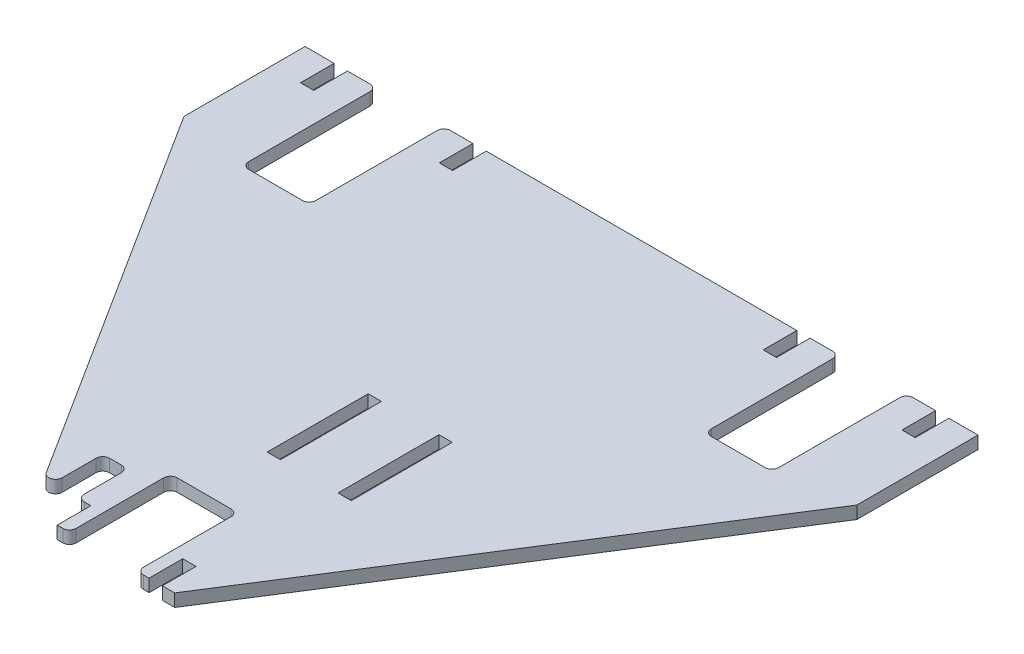
SolidWorks part; units mm, degrees
material "Corrugated Paper"
ref_plane "Front Plane" through (0, 0, 0) normal (0, 0, 1) x (1, 0, 0)
ref_plane "Top Plane" through (0, 0, 0) normal (0, 1, 0) x (1, 0, 0)
ref_plane "Right Plane" through (0, 0, 0) normal (1, 0, 0) x (0, 0, -1)
sketch "Sketch1" plane through (0, 0, 0) normal (0, 1, 0) x (1, 0, 0)
  line L0 (0, 0) -> (0, -142.875) construction
  line L1 (12.7, -63.5) -> (-12.7, -63.5)
  line L2 (-12.7, -63.5) -> (-12.7, -101.6)
  line L3 (-12.7, -101.6) -> (-17.3355, -101.6)
  line L4 (-26.9875, -101.6) -> (-127, 55.88)
  line L5 (-127, 55.88) -> (-127, 101.6)
  line L6 (-127, 101.6) -> (-116.0145, 101.6)
  line L7 (-100.0125, 101.6) -> (-100.0125, 50.8)
  line L9 (-100.0125, 50.8) -> (-74.6125, 50.8)
  line L10 (-74.6125, 50.8) -> (-74.6125, 101.6)
  line L11 (-74.6125, 101.6) -> (-63.627, 101.6)
  line L13 (74.6125, 50.8) -> (74.6125, 101.6)
  line L14 (100.0125, 50.8) -> (74.6125, 50.8)
  line L15 (100.0125, 101.6) -> (100.0125, 50.8)
  line L16 (127, 101.6) -> (116.0145, 101.6)
  line L17 (127, 55.88) -> (127, 101.6)
  line L18 (26.9875, -101.6) -> (127, 55.88)
  line L19 (12.7, -101.6) -> (17.3355, -101.6)
  line L20 (12.7, -63.5) -> (12.7, -101.6)
  line L21 (-127, 101.6) -> (127, -101.6) construction
  line L22 (-22.352, -101.6) -> (-26.9875, -101.6)
  line L24 (-22.352, -101.6) -> (-22.352, -88.9)
  line L25 (-22.352, -88.9) -> (-17.3355, -88.9)
  line L26 (-17.3355, -101.6) -> (-17.3355, -88.9)
  line L27 (22.352, -101.6) -> (22.352, -88.9)
  line L28 (22.352, -88.9) -> (17.3355, -88.9)
  line L29 (17.3355, -101.6) -> (17.3355, -88.9)
  line L30 (22.352, -101.6) -> (26.9875, -101.6)
  line L31 (-87.3125, 50.8) -> (-87.3125, 101.6) construction
  line L32 (-110.998, 101.6) -> (-100.0125, 101.6)
  line L34 (-116.0145, 101.6) -> (-116.0145, 88.9)
  line L35 (-116.0145, 88.9) -> (-110.998, 88.9)
  line L36 (-110.998, 101.6) -> (-110.998, 88.9)
  line L37 (-58.6105, 101.6) -> (-58.6105, 88.9)
  line L38 (-58.6105, 88.9) -> (-63.627, 88.9)
  line L39 (-63.627, 101.6) -> (-63.627, 88.9)
  line L40 (-58.6105, 101.6) -> (58.6105, 101.6)
  line L41 (116.0145, 101.6) -> (116.0145, 88.9)
  line L42 (116.0145, 88.9) -> (110.998, 88.9)
  line L43 (110.998, 101.6) -> (110.998, 88.9)
  line L44 (58.6105, 101.6) -> (58.6105, 88.9)
  line L45 (63.627, 101.6) -> (63.627, 88.9)
  line L46 (58.6105, 88.9) -> (63.627, 88.9)
  line L47 (63.627, 101.6) -> (74.6125, 101.6)
  line L48 (110.998, 101.6) -> (100.0125, 101.6)
  point P26 (0, -63.5)
  dimension "D2" = 25.4
  dimension "D3" = 254
  dimension "D5" = 38.1
  dimension "D6" = 50.8
  dimension "D7" = 203.2
  dimension "D8" = 45.72
  dimension "D9" = 26.9875
  dimension "D4" = 14.2875
  dimension "D10" = 5.0165
  dimension "D11" = 12.7
  dimension "D12" = 5.0165
extrude "Boss-Extrude1" add sketch "Sketch1" along normal blind 4.7625 contours L13 L47 L45 L46 L44 L40 L37 L38 L39 L11 L10 L9 L7 L32 L36 L35 L34 L6 L5 L4 L22 L24 L25 L26 L3 L2 L1 L20 L19 L29 L28 L27 L30 L18 L17 L16 L41 L42 L43 L48 L15 L14
sketch "Sketch2" plane through (0, 4.7625, 0) normal (0, 1, 0) x (1, 0, 0)
  line L0 (14.2875, 0) -> (14.2875, 54.8341) construction
  line L6 (-58.6105, 88.9) -> (-63.627, 88.9) construction
  line L7 (-1.5875, 0) -> (3.429, 0)
  line L8 (-1.5875, 0) -> (-1.5875, -38.1)
  line L9 (-1.5875, -38.1) -> (3.429, -38.1)
  line L10 (3.429, 0) -> (3.429, -38.1)
  line L11 (-22.352, -101.6) -> (-31.877, -101.6)
  line L12 (25.146, 0) -> (25.146, -38.1)
  line L13 (30.1625, -38.1) -> (25.146, -38.1)
  line L14 (30.1625, 0) -> (30.1625, -38.1)
  line L15 (30.1625, 0) -> (25.146, 0)
  line L16 (-22.352, -101.6) -> (-22.352, -69.85)
  line L17 (12.7, -63.5) -> (-12.7, -63.5) construction
  line L18 (-22.352, -69.85) -> (-31.877, -69.85)
  line L19 (-31.877, -101.6) -> (-31.877, -69.85)
  dimension "D2" = 25.4
  dimension "D4" = 14.2875
  dimension "D3" = 31.75
  dimension "D1" = 38.1
  dimension "D5" = 9.525
  dimension "D6" = 31.75
extrude "Cut-Extrude1" cut sketch "Sketch2" against normal through all
fillet "Fillet1" radius 2.54 4 edges at (-22.352, 2.3813, 88.9) (-31.877, 2.3813, 93.901) (-22.352, 2.3813, 69.85) (-31.877, 2.3813, 69.85)
fillet "Fillet2" radius 2.54 12 edges at (-12.7, 2.3813, 101.6) (12.7, 2.3813, 101.6) (12.7, 2.3813, 63.5) (-12.7, 2.3813, 63.5) (100.0125, 2.3813, -101.6) (100.0125, 2.3813, -50.8) (74.6125, 2.3813, -101.6) (74.6125, 2.3813, -50.8) (-100.0125, 2.3813, -101.6) (-74.6125, 2.3813, -101.6) (-74.6125, 2.3813, -50.8) (-100.0125, 2.3813, -50.8)
equation "\"D1@Boss-Extrude1\" = \"thick\""
equation "\"D4@Sketch1\" = \"thick\" * 3"
equation "\"D10@Sketch1\"=\"thick\"+\"clear\""
equation "\"D9@Sketch1\" = \"thick\" * 3 + 0.5"
equation "\"D12@Sketch1\"=\"thick\"+\"clear\""
equation "\"D3@Sketch2\"=\"MotorLength@Motor-1.Part\""
equation "\"D1@Sketch2\" =  ( \"MotorDiameter@Motor-1.Part\" + 0.5 ) "
equation "\"D4@Sketch2\"= 3 * \"thick\""
equation "\"rodThick\"= 0.1in"
equation "\"thick\"= 3/16in"
equation "\"D5@Sketch2\"=2*\"thick\""
equation "\"clear\"= 0.01in"
